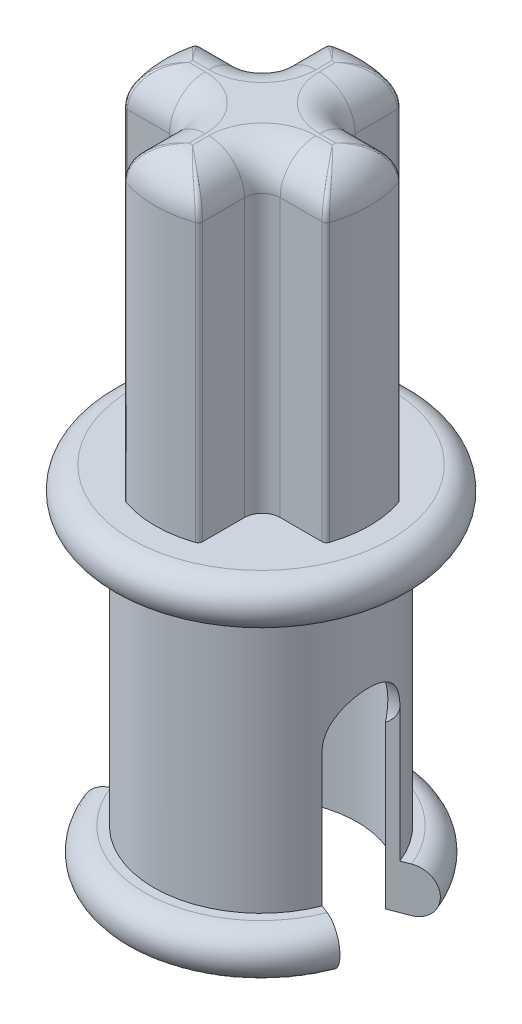
SolidWorks part; units mm, degrees
ref_plane "Front Plane" through (0, 0, 0) normal (0, 0, 1) x (1, 0, 0)
ref_plane "Top Plane" through (0, 0, 0) normal (0, 1, 0) x (1, 0, 0)
ref_plane "Right Plane" through (0, 0, 0) normal (1, 0, 0) x (0, 0, -1)
sketch "Sketch1" plane through (0, 0, 0) normal (0, 1, 0) x (1, 0, 0)
  circle A0 centre (0, 0) radius 3.4
  dimension "D1" = 6.8
extrude "Boss-Extrude1" add sketch "Sketch1" along normal mid plane 1
fillet "Fillet3" 2 edges at (0, 0.5, 3.4) (0, -0.5, 3.4) type full round first side face at (0, 0.5, 3.4) second side face at (0, -0.5, 3.4) middle face at (0, 0.5, 3.4)
sketch "Sketch2" plane through (0, 0.5, 0) normal (0, 1, 0) x (1, 0, 0)
  line L0 (-0.84, -1.2115) -> (-0.84, -2.1492)
  line L1 (-0.84, 2.2062) -> (-0.84, 1.2685)
  line L2 (0.84, 2.2062) -> (0.84, 1.2685)
  line L3 (-0.84, 2.2767) -> (0.84, -2.2197) construction
  line L4 (-0.84, -2.2197) -> (0.84, 2.2767) construction
  line L5 (-2.1777, 0.8685) -> (-1.24, 0.8685)
  line L6 (-2.1777, -0.8115) -> (-1.24, -0.8115)
  line L7 (-2.2482, 0.8685) -> (2.2482, -0.8115) construction
  line L8 (-2.2482, -0.8115) -> (2.2482, 0.8685) construction
  line L9 (1.24, 0.8685) -> (2.1777, 0.8685)
  line L10 (0.84, -1.2115) -> (0.84, -2.1492)
  line L11 (1.24, -0.8115) -> (2.1777, -0.8115)
  arc A0 (0.7722, 2.3009) -> (-0.7722, 2.3009) centre (0, 0.0285) ccw
  arc A1 (-2.2724, 0.8007) -> (-2.2724, -0.7437) centre (0, 0.0285) ccw
  arc A2 (2.2724, -0.7437) -> (2.2724, 0.8007) centre (0, 0.0285) ccw
  arc A3 (-0.7722, -2.2439) -> (0.7722, -2.2439) centre (0, 0.0285) ccw
  arc A4 (-2.1777, 0.8685) -> (-2.2724, 0.8007) centre (-2.1777, 0.7685) ccw
  arc A5 (-2.2724, -0.7437) -> (-2.1777, -0.8115) centre (-2.1777, -0.7115) ccw
  arc A6 (-0.84, -2.1492) -> (-0.7722, -2.2439) centre (-0.74, -2.1492) ccw
  arc A7 (0.7722, -2.2439) -> (0.84, -2.1492) centre (0.74, -2.1492) ccw
  arc A8 (2.1777, -0.8115) -> (2.2724, -0.7437) centre (2.1777, -0.7115) ccw
  arc A9 (2.1777, 0.8685) -> (2.2724, 0.8007) centre (2.1777, 0.7685) cw
  arc A10 (0.7722, 2.3009) -> (0.84, 2.2062) centre (0.74, 2.2062) cw
  arc A11 (-0.7722, 2.3009) -> (-0.84, 2.2062) centre (-0.74, 2.2062) ccw
  arc A12 (-0.84, -1.2115) -> (-1.24, -0.8115) centre (-1.24, -1.2115) ccw
  arc A13 (0.84, -1.2115) -> (1.24, -0.8115) centre (1.24, -1.2115) cw
  arc A14 (1.24, 0.8685) -> (0.84, 1.2685) centre (1.24, 1.2685) cw
  arc A15 (-1.24, 0.8685) -> (-0.84, 1.2685) centre (-1.24, 1.2685) ccw
extrude "Boss-Extrude2" add sketch "Sketch2" along normal blind 7
fillet "Fillet4" radius 0.8 24 edges at (-1.7089, 7.5, -0.8685) (-0.9572, 7.5, -0.9857) (-0.84, 7.5, -1.7374) (-0.8213, 7.5, -2.2644) (0, 7.5, -2.4285) (0.8213, 7.5, -2.2644) (0.84, 7.5, -1.7374) (0.9572, 7.5, -0.9857) (1.7089, 7.5, -0.8685) (2.2359, 7.5, -0.8498) (2.4, 7.5, -0.0285) (2.2359, 7.5, 0.7928) (1.7089, 7.5, 0.8115) (0.9572, 7.5, 0.9287) (0.84, 7.5, 1.6804) (0.8213, 7.5, 2.2074) (0, 7.5, 2.3715) (-0.8213, 7.5, 2.2074) (-0.84, 7.5, 1.6804) (-0.9572, 7.5, 0.9287) (-1.7089, 7.5, 0.8115) (-2.2359, 7.5, 0.7928) (-2.4, 7.5, -0.0285) (-2.2359, 7.5, -0.8498)
sketch "Sketch3" plane through (0, -0.5, 0) normal (0, -1, 0) x (1, 0, 0)
  circle A0 centre (0, 0) radius 2.4
  circle A1 centre (0, 0) radius 2.15
  dimension "D1" = 4.8
  dimension "D2" = 4.3
extrude "Boss-Extrude3" add sketch "Sketch3" along normal blind 6
sketch "Sketch4" plane through (0, -6.5, 0) normal (0, -1, 0) x (1, 0, 0)
  circle A0 centre (0, 0) radius 3.1
  circle A1 centre (0, 0) radius 2.15
  dimension "D1" = 6.2
extrude "Boss-Extrude4" add sketch "Sketch4" along normal blind 1
sketch "Sketch5" plane through (0, -7.5, 0) normal (0, -1, 0) x (1, 0, 0)
  line L0 (2.0038, 0.7793) -> (2.8892, 1.1236)
  line L1 (2.0038, -0.7793) -> (2.8892, -1.1236)
  line L2 (-2.0038, 0.7793) -> (-2.8892, 1.1236)
  line L3 (-2.0038, -0.7793) -> (-2.8892, -1.1236)
  circle A0 centre (0, 0) radius 3.1 construction
  arc A1 (-2.8892, -1.1236) -> (-2.8892, 1.1236) centre (0, 0) cw
  arc A2 (-2.0038, 0.7793) -> (-2.0038, -0.7793) centre (0, 0) ccw
  circle A3 centre (0, 0) radius 2.15 construction
  circle A4 centre (0, 0) radius 2.15 construction
  arc A5 (2.0038, 0.7793) -> (2.0038, -0.7793) centre (0, 0) cw
  arc A6 (2.8892, 1.1236) -> (2.8892, -1.1236) centre (0, 0) cw
  point P4 (0, 0)
  point P11 (0, 0)
  point P18 (0, 0)
  point P25 (0, 0)
  point P28 (0, 0)
  point P31 (0, 0)
  dimension "D1" = 0.95
extrude "Cut-Extrude1" cut sketch "Sketch5" against normal blind 4
sketch "Sketch6" plane through (0, 0, 0) normal (1, 0, 0) x (0, 0, -1)
  line L0 (-0.8699, -3.5) -> (0.8699, -3.5) construction
  circle A0 centre (0, -3.5) radius 0.8699
extrude "Cut-Extrude2" cut sketch "Sketch6" against normal mid plane 5
fillet "Fillet7" 2 edges at (0, -7.5, -3.1) (0, -6.5, -3.1) type full round first side face at (0, -7.5, -1.7882) second side face at (0, -6.5, -1.8734) middle face at (0, -7, -2.1118)
fillet "Fillet8" 2 edges at (0, -7.5, 3.1) (0, -6.5, 3.1) type full round first side face at (0, -7.5, 1.7882) second side face at (0, -6.5, 1.8734) middle face at (0, -7, 2.1118)
